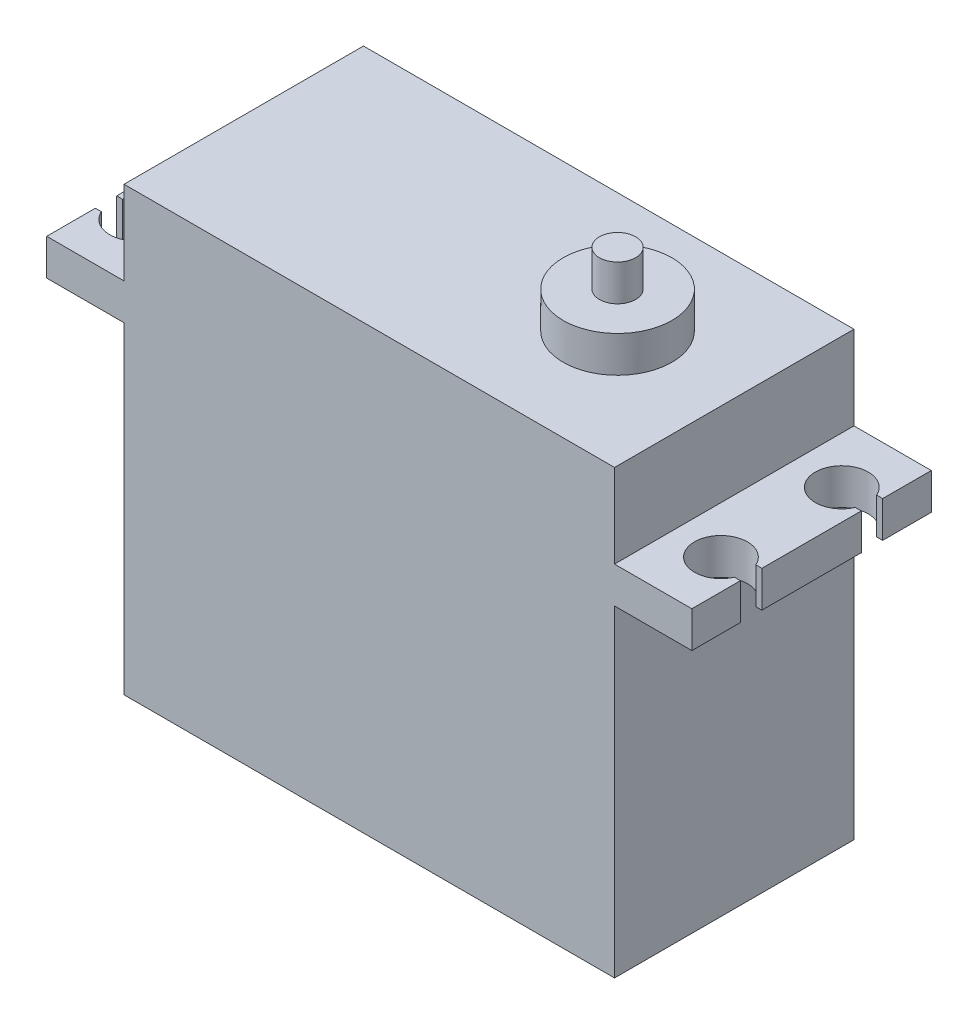
SolidWorks part; units mm, degrees
ref_plane "Plan de face" through (0, 0, 0) normal (0, 0, 1) x (1, 0, 0)
ref_plane "Plan de dessus" through (0, 0, 0) normal (0, 1, 0) x (1, 0, 0)
ref_plane "Plan de droite" through (0, 0, 0) normal (1, 0, 0) x (0, 0, -1)
sketch "Esquisse2" plane through (0, 0, 0) normal (0, 1, 0) x (1, 0, 0)
  line L1 (-5.7906, -5.6198) -> (-46.3906, -5.6198)
  line L2 (-5.7906, -5.6198) -> (-5.7906, -25.4398)
  line L3 (-5.7906, -25.4398) -> (-46.3906, -25.4398)
  line L4 (-46.3906, -5.6198) -> (-46.3906, -25.4398)
  line L5 (-5.7906, -5.6198) -> (-46.3906, -25.4398) construction
  line L6 (-5.7906, -25.4398) -> (-46.3906, -5.6198) construction
  point P0 (-26.0906, -15.5298)
  dimension "D1" = 19.82
  dimension "D2" = 40.6
extrude "Boss.-Extru.1" add sketch "Esquisse2" along normal blind 36.6
sketch "Esquisse5" plane through (0, 36.6, 0) normal (0, 1, 0) x (1, 0, 0)
  line L0 (-15.4506, -5.6198) -> (-15.4506, -25.4398) construction
  line L1 (-5.7906, -5.6198) -> (-46.3906, -5.6198) construction
  line L2 (-46.3906, -25.4398) -> (-5.7906, -25.4398) construction
  circle A0 centre (-15.4506, -15.5298) radius 4.5
  circle A1 centre (-15.4506, -15.5298) radius 1.5
  point P6 (-15.4506, -15.5298)
  dimension "D2" = 9
  dimension "D3" = 3
  dimension "D1" = 9.66
extrude "Boss.-Extru.2" add sketch "Esquisse5" along normal blind 6 contours A1 L0 | L0 A1 region at (-14.814, 36.6, 15.5298) region at (-16.0873, 36.6, 15.5298)
ref_plane "Plan1" through (0, 26.67, 0) normal (0, -1, 0) x (-1, 0, 0)
sketch "Esquisse12" plane through (0, 26.67, 0) normal (0, -1, 0) x (-1, 0, 0)
  line L0 (5.7906, -25.4398) -> (46.3906, -5.6198) construction
  line L1 (52.7906, -25.4398) -> (46.3906, -25.4398)
  line L2 (52.7906, -25.4398) -> (52.7906, -5.6198)
  line L3 (52.7906, -5.6198) -> (46.3906, -5.6198)
  line L4 (46.3906, -25.4398) -> (46.3906, -5.6198)
  line L5 (1.8906, -10.5298) -> (50.2906, -20.5298) construction
  line L6 (1.8906, -20.5298) -> (50.2906, -20.5298)
  line L7 (5.7906, -5.6198) -> (-0.6094, -5.6198)
  line L8 (5.7906, -5.6198) -> (5.7906, -25.4398)
  line L9 (5.7906, -25.4398) -> (-0.6094, -25.4398)
  line L10 (-0.6094, -5.6198) -> (-0.6094, -25.4398)
  line L11 (1.8906, -20.5298) -> (1.8906, -10.5298)
  line L12 (1.8906, -10.5298) -> (50.2906, -10.5298)
  line L13 (52.294, -19.645) -> (52.294, -21.4146)
  line L14 (50.2906, -5.6198) -> (50.2906, -25.4398) construction
  line L15 (50.2906, -20.5298) -> (50.2906, -10.5298)
  line L16 (52.294, -19.645) -> (52.7906, -19.645)
  line L17 (52.294, -21.4146) -> (52.7906, -21.4146)
  line L18 (52.7906, -19.645) -> (52.7906, -21.4146)
  line L19 (52.294, -9.645) -> (52.294, -11.4146)
  line L20 (52.294, -9.645) -> (52.7906, -9.645)
  line L21 (52.294, -11.4146) -> (52.7906, -11.4146)
  line L22 (52.7906, -9.645) -> (52.7906, -11.4146)
  line L23 (-0.1127, -9.645) -> (-0.1127, -11.4146)
  line L24 (-0.1127, -9.645) -> (-0.6094, -9.645)
  line L25 (-0.1127, -11.4146) -> (-0.6094, -11.4146)
  line L26 (-0.6094, -9.645) -> (-0.6094, -11.4146)
  line L27 (-0.1127, -21.4146) -> (-0.1127, -19.645)
  line L28 (-0.1127, -21.4146) -> (-0.6094, -21.4146)
  line L29 (-0.1127, -19.645) -> (-0.6094, -19.645)
  line L30 (-0.6094, -21.4146) -> (-0.6094, -19.645)
  circle A0 centre (50.2906, -10.5298) radius 2.19
  circle A1 centre (50.2906, -20.5298) radius 2.19
  circle A2 centre (1.8906, -10.5298) radius 2.19
  circle A3 centre (1.8906, -20.5298) radius 2.19
  point P0 (26.0906, -15.5298)
  point P14 (26.0906, -15.5298)
  dimension "D3" = 4.38
  dimension "D4" = 10
  dimension "D1" = 53.4
  dimension "D2" = 48.4
extrude "Boss.-Extru.3" add sketch "Esquisse12" against normal blind 3 contours A1 L16 L2 L21 A0 L15 | A1 L15 A0 L12 L4 L6 | A0 L20 L2 L3 L4 L12 | A1 L6 L4 L1 L2 L17 | A3 L6 L8 L12 A2 L11 | A3 L11 A2 L25 L10 L29 | A3 L28 L10 L9 L8 L6 | A2 L12 L8 L7 L10 L24 region at (-49.3249, 26.67, 23.5001) region at (-48.0963, 26.67, 15.5298) region at (-51.6429, 26.67, 15.5298) region at (-49.3249, 26.67, 7.5595) region at (-2.8564, 26.67, 23.5001) region at (-4.085, 26.67, 15.5298) region at (-2.8564, 26.67, 7.5595) region at (-0.5384, 26.67, 15.5298)
extrude "Boss.-Extru.4" add sketch "Esquisse5<3>" along normal blind 3
sketch "Esquisse5<3>" plane through (0, 36.6, 0) normal (0, 1, 0) x (1, 0, 0) same geometry as "Esquisse5"
